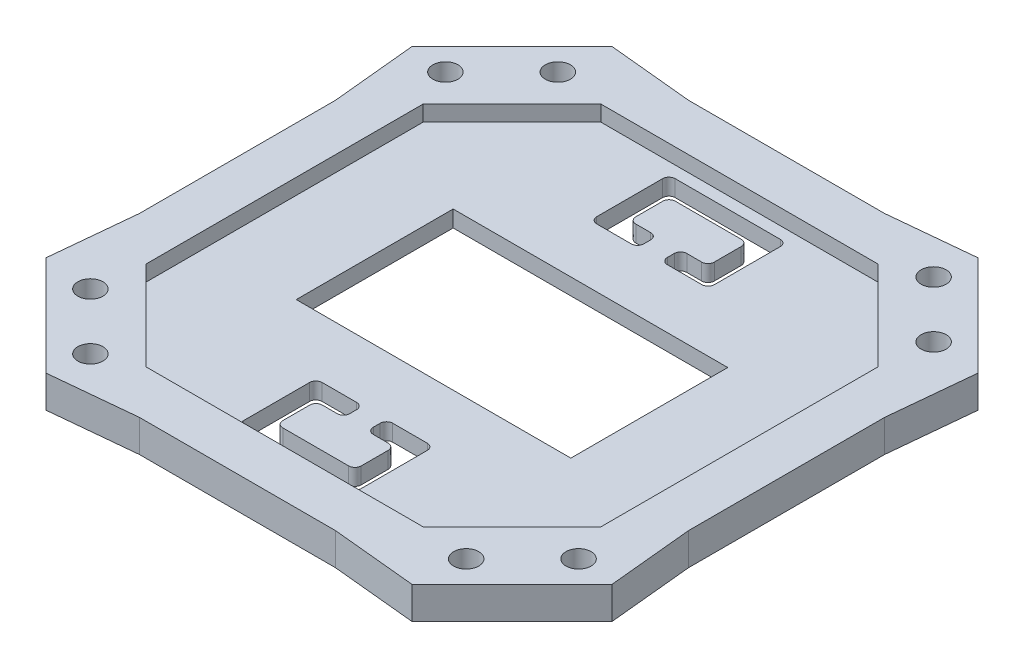
SolidWorks part; units mm, degrees
ref_plane "Front Plane" through (0, 0, 0) normal (0, 0, 1) x (1, 0, 0)
ref_plane "Top Plane" through (0, 0, 0) normal (0, 1, 0) x (1, 0, 0)
ref_plane "Right Plane" through (0, 0, 0) normal (1, 0, 0) x (0, 0, -1)
sketch "Sketch1" plane through (0, 0, 0) normal (0, 1, 0) x (1, 0, 0)
  line L0 (0, 0) -> (84.8528, 84.8528) construction
  line L1 (35, -35) -> (-35, -35) construction
  line L2 (35, -35) -> (35, 35) construction
  line L3 (35, 35) -> (-35, 35) construction
  line L4 (-35, -35) -> (-35, 35) construction
  line L5 (35, -35) -> (-35, 35) construction
  line L6 (35, 35) -> (-35, -35) construction
  line L7 (0, 35) -> (0, -35) construction
  line L8 (-12.5, 35) -> (12.5, 35)
  line L9 (35, 12.5) -> (35, -12.5)
  line L10 (12.5, -35) -> (-12.5, -35)
  line L11 (-35, -12.5) -> (-35, 12.5)
  line L12 (20.5061, 33.234) -> (33.234, 20.5061) construction
  line L13 (23.3345, 36.0624) -> (36.0624, 23.3345)
  line L14 (12.5, 35) -> (23.3345, 36.0624)
  line L15 (36.0624, 23.3345) -> (35, 12.5)
  line L16 (36.0624, -23.3345) -> (23.3345, -36.0624)
  line L17 (35, -12.5) -> (36.0624, -23.3345)
  line L18 (23.3345, -36.0624) -> (12.5, -35)
  line L19 (-23.3345, -36.0624) -> (-36.0624, -23.3345)
  line L20 (-12.5, -35) -> (-23.3345, -36.0624)
  line L21 (-36.0624, -23.3345) -> (-35, -12.5)
  line L22 (-36.0624, 23.3345) -> (-23.3345, 36.0624)
  line L23 (-35, 12.5) -> (-36.0624, 23.3345)
  line L24 (-23.3345, 36.0624) -> (-12.5, 35)
  circle A0 centre (22.6274, 31.1127) radius 1.6
  circle A1 centre (29.7906, 23.9496) radius 1.6
  circle A2 centre (31.1127, -22.6274) radius 1.6
  circle A3 centre (23.9496, -29.7906) radius 1.6
  circle A4 centre (-22.6274, -31.1127) radius 1.6
  circle A5 centre (-29.7906, -23.9496) radius 1.6
  circle A6 centre (-31.1127, 22.6274) radius 1.6
  circle A7 centre (-23.9496, 29.7906) radius 1.6
  point P0 (0, 0)
  dimension "D7" = 3.2
  dimension "D8" = 6
  dimension "D1" = 70
  dimension "D2" = 70
  dimension "D3" = 120
  dimension "D4" = 25
  dimension "D5" = 12.5
  dimension "D9" = 82
  dimension "D10" = 4
  dimension "D11" = 18
  dimension "D12" = 4.1302
  dimension "D6" = 4
  dimension "D13" = 4
extrude "Boss-Extrude2" add sketch "Sketch1" along normal blind 4.1
sketch "Sketch2" plane through (0, 4.1, 0) normal (0, 1, 0) x (1, 0, 0)
  line L0 (0, 35) -> (0, 0) construction
  line L1 (0, 0) -> (-35, 0) construction
  line L2 (-35, -12.5) -> (-35, 12.5) construction
  line L3 (-17.669, 29) -> (17.669, 29)
  line L4 (17.669, 29) -> (29, 17.669)
  line L5 (29, 17.669) -> (29, -17.669)
  line L6 (29, -17.669) -> (17.669, -29)
  line L7 (17.669, -29) -> (-17.669, -29)
  line L8 (-17.669, -29) -> (-29, -17.669)
  line L9 (-29, -17.669) -> (-29, 17.669)
  line L10 (-29, 17.669) -> (-17.669, 29)
  line L12 (-23.3345, -36.0624) -> (-36.0624, -23.3345) construction
  line L13 (23.3345, 36.0624) -> (36.0624, 23.3345) construction
  line L14 (36.0624, -23.3345) -> (23.3345, -36.0624) construction
  line L16 (-36.0624, 23.3345) -> (-23.3345, 36.0624) construction
  line L17 (12.5, -35) -> (-12.5, -35) construction
  line L18 (-12.5, 35) -> (12.5, 35) construction
  dimension "D1" = 6
  dimension "D2" = 9
extrude "Cut-Extrude1" cut sketch "Sketch2" against normal blind 2
sketch "Sketch4" plane through (0, 2.1, 0) normal (0, 1, 0) x (1, 0, 0)
  line L0 (0, 29) -> (0, 0) construction
  line L1 (17.669, 29) -> (-17.669, 29) construction
  line L2 (0, 0) -> (-29, 0) construction
  line L3 (-29, 17.669) -> (-29, -17.669) construction
  line L4 (-24.0792, 13.5676) -> (-16.0792, 6.8995)
  line L5 (-15, 4.5951) -> (-15, -4.5951)
  line L6 (-16.0792, -6.8995) -> (-24.0792, -13.5676)
  line L7 (-29, -11.2631) -> (-29, 11.2631)
  line L8 (-6.8995, 16.0792) -> (-13.5676, 24.0792)
  line L9 (4.5951, 15) -> (-4.5951, 15)
  line L10 (13.5676, 24.0792) -> (6.8995, 16.0792)
  line L11 (-11.2631, 29) -> (11.2631, 29)
  line L12 (16.0792, 6.8995) -> (24.0792, 13.5676)
  line L13 (15, -4.5951) -> (15, 4.5951)
  line L14 (24.0792, -13.5676) -> (16.0792, -6.8995)
  line L15 (29, 11.2631) -> (29, -11.2631)
  line L16 (6.8995, -16.0792) -> (13.5676, -24.0792)
  line L17 (-4.5951, -15) -> (4.5951, -15)
  line L18 (-13.5676, -24.0792) -> (-6.8995, -16.0792)
  line L19 (11.2631, -29) -> (-11.2631, -29)
  arc A0 (-15, -4.5951) -> (-16.0792, -6.8995) centre (-18, -4.5951) cw
  arc A1 (-16.0792, 6.8995) -> (-15, 4.5951) centre (-18, 4.5951) cw
  arc A2 (-24.0792, -13.5676) -> (-29, -11.2631) centre (-26, -11.2631) cw
  arc A3 (-24.0792, 13.5676) -> (-29, 11.2631) centre (-26, 11.2631) ccw
  arc A4 (-4.5951, 15) -> (-6.8995, 16.0792) centre (-4.5951, 18) cw
  arc A5 (6.8995, 16.0792) -> (4.5951, 15) centre (4.5951, 18) cw
  arc A6 (13.5676, 24.0792) -> (11.2631, 29) centre (11.2631, 26) ccw
  arc A7 (-13.5676, 24.0792) -> (-11.2631, 29) centre (-11.2631, 26) cw
  arc A8 (15, 4.5951) -> (16.0792, 6.8995) centre (18, 4.5951) cw
  arc A9 (16.0792, -6.8995) -> (15, -4.5951) centre (18, -4.5951) cw
  arc A10 (24.0792, -13.5676) -> (29, -11.2631) centre (26, -11.2631) ccw
  arc A11 (24.0792, 13.5676) -> (29, 11.2631) centre (26, 11.2631) cw
  arc A12 (4.5951, -15) -> (6.8995, -16.0792) centre (4.5951, -18) cw
  arc A13 (-6.8995, -16.0792) -> (-4.5951, -15) centre (-4.5951, -18) cw
  arc A14 (-13.5676, -24.0792) -> (-11.2631, -29) centre (-11.2631, -26) ccw
  arc A15 (13.5676, -24.0792) -> (11.2631, -29) centre (11.2631, -26) cw
  point P16 (-15, -6)
  point P19 (-15, 6)
  point P22 (-29, -17.669)
  point P25 (-29, 17.669)
  dimension "D4" = 3
  dimension "D1" = 12
  dimension "D2" = 15
  dimension "D3" = 6
  dimension "D5" = 4
extrude "Cut-Extrude2" [suppressed] cut sketch "Sketch4" against normal blind 1.5
sketch "Sketch6" plane through (0, 2.1, 0) normal (0, 1, 0) x (1, 0, 0)
  line L0 (0, 0) -> (84.8528, 84.8528) construction
  line L1 (0, 0) -> (15.25, 0) construction
  line L2 (0, 0) -> (0, 15.25) construction
  line L3 (0, 15.25) -> (15.25, 15.25) construction
  line L4 (15.25, 0) -> (15.25, 15.25) construction
  circle A0 centre (15.25, 15.25) radius 1.5
  dimension "D2" = 3
  dimension "D1" = 15.25
extrude "Cut-Extrude3" [suppressed] cut sketch "Sketch6" against normal through all contours A0
sketch "Sketch7" [suppressed] plane through (0, 2, 0) normal (0, 1, 0) x (1, 0, 0)
  circle A0 centre (15.25, 15.25) radius 4
  circle A1 centre (15.25, 15.25) radius 1.5 construction
  circle A2 centre (15.25, 15.25) radius 1.5
  dimension "D1" = 8
extrude "Boss-Extrude3" [suppressed] add sketch "Sketch7" along normal blind 1.5
ref_axis "Axis1" [suppressed] through (0, 4.2, 0) along (0, -1, 0)
pattern_circular "CirPattern1" [suppressed] count 4 over 360 about axis through (0, 4.2, 0) along (0, -1, 0) of bodies 106
fillet "Fillet1" [suppressed] radius 2
sketch "Sketch8" plane through (0, 2.1, 0) normal (0, 1, 0) x (1, 0, 0)
  line L0 (0, -29) -> (0, 29) construction
  line L2 (0, 0) -> (-23.4448, 0) construction
  line L3 (17.669, 29) -> (-17.669, 29) construction
  line L9 (-1.5, 19.1817) -> (-1.5, 18.3)
  line L14 (-6.7, 27.5) -> (6.7, 27.5)
  line L15 (-7.5, 26.7) -> (-7.5, 18.3)
  line L16 (-6.7, 17.5) -> (-2.3, 17.5)
  line L17 (7.5, 26.7) -> (7.5, 18.3)
  line L18 (-7.5, 27.5) -> (7.5, 17.5) construction
  line L19 (-7.5, 17.5) -> (7.5, 27.5) construction
  line L20 (-4.2, 25.0183) -> (4.2, 25.0183)
  line L21 (-5, 24.2183) -> (-5, 20.7817)
  line L22 (-4.2, 19.9817) -> (-2.3, 19.9817)
  line L23 (5, 24.2183) -> (5, 20.7817)
  line L24 (-5, 25.0183) -> (5, 19.9817) construction
  line L25 (-5, 19.9817) -> (5, 25.0183) construction
  line L26 (1.5, 19.1817) -> (1.5, 18.3)
  line L27 (2.3, 19.9817) -> (4.2, 19.9817)
  line L28 (2.3, 17.5) -> (6.7, 17.5)
  line L29 (-5, -19.9817) -> (5, -25.0183) construction
  line L30 (-5, -25.0183) -> (5, -19.9817) construction
  line L31 (-7.5, -17.5) -> (7.5, -27.5) construction
  line L32 (-7.5, -27.5) -> (7.5, -17.5) construction
  line L33 (2.3, -17.5) -> (6.7, -17.5)
  line L34 (2.3, -19.9817) -> (4.2, -19.9817)
  line L35 (1.5, -19.1817) -> (1.5, -18.3)
  line L36 (5, -24.2183) -> (5, -20.7817)
  line L37 (-4.2, -19.9817) -> (-2.3, -19.9817)
  line L38 (-5, -24.2183) -> (-5, -20.7817)
  line L39 (-4.2, -25.0183) -> (4.2, -25.0183)
  line L40 (7.5, -26.7) -> (7.5, -18.3)
  line L41 (-6.7, -17.5) -> (-2.3, -17.5)
  line L42 (-7.5, -26.7) -> (-7.5, -18.3)
  line L43 (-6.7, -27.5) -> (6.7, -27.5)
  line L44 (-1.5, -19.1817) -> (-1.5, -18.3)
  arc A0 (1.5, 18.3) -> (2.3, 17.5) centre (2.3, 18.3) ccw
  arc A1 (1.5, 19.1817) -> (2.3, 19.9817) centre (2.3, 19.1817) cw
  arc A2 (-1.5, 18.3) -> (-2.3, 17.5) centre (-2.3, 18.3) cw
  arc A3 (4.2, 25.0183) -> (5, 24.2183) centre (4.2, 24.2183) cw
  arc A4 (-5, 20.7817) -> (-4.2, 19.9817) centre (-4.2, 20.7817) ccw
  arc A5 (-4.2, 25.0183) -> (-5, 24.2183) centre (-4.2, 24.2183) ccw
  arc A10 (4.2, 19.9817) -> (5, 20.7817) centre (4.2, 20.7817) ccw
  arc A11 (-1.5, 19.1817) -> (-2.3, 19.9817) centre (-2.3, 19.1817) ccw
  arc A12 (6.7, 27.5) -> (7.5, 26.7) centre (6.7, 26.7) cw
  arc A13 (-7.5, 18.3) -> (-6.7, 17.5) centre (-6.7, 18.3) ccw
  arc A14 (-6.7, 27.5) -> (-7.5, 26.7) centre (-6.7, 26.7) ccw
  arc A15 (6.7, 17.5) -> (7.5, 18.3) centre (6.7, 18.3) ccw
  arc A16 (6.7, -17.5) -> (7.5, -18.3) centre (6.7, -18.3) cw
  arc A17 (-6.7, -27.5) -> (-7.5, -26.7) centre (-6.7, -26.7) cw
  arc A18 (-7.5, -18.3) -> (-6.7, -17.5) centre (-6.7, -18.3) cw
  arc A19 (6.7, -27.5) -> (7.5, -26.7) centre (6.7, -26.7) ccw
  arc A20 (-1.5, -19.1817) -> (-2.3, -19.9817) centre (-2.3, -19.1817) cw
  arc A21 (4.2, -19.9817) -> (5, -20.7817) centre (4.2, -20.7817) cw
  arc A22 (-4.2, -25.0183) -> (-5, -24.2183) centre (-4.2, -24.2183) cw
  arc A23 (-5, -20.7817) -> (-4.2, -19.9817) centre (-4.2, -20.7817) cw
  arc A24 (4.2, -25.0183) -> (5, -24.2183) centre (4.2, -24.2183) ccw
  arc A25 (-1.5, -18.3) -> (-2.3, -17.5) centre (-2.3, -18.3) ccw
  arc A26 (1.5, -19.1817) -> (2.3, -19.9817) centre (2.3, -19.1817) ccw
  arc A27 (1.5, -18.3) -> (2.3, -17.5) centre (2.3, -18.3) cw
  point P0 (0, 22.5)
  point P12 (0, 22.5)
  point P22 (1.5, 17.5)
  point P25 (1.5, 19.9817)
  point P28 (-1.5, 17.5)
  point P43 (-1.5, 19.9817)
  point P101 (-1.5, -19.9817)
  point P102 (-1.5, -17.5)
  point P103 (1.5, -19.9817)
  point P104 (1.5, -17.5)
  point P105 (0, -22.5)
  dimension "D6" = 0.8
  dimension "D1" = 17.5
  dimension "D2" = 10
  dimension "D3" = 15
  dimension "D4" = 2.5
  dimension "D5" = 6
extrude "Cut-Extrude4" cut sketch "Sketch8" against normal through all
sketch "Sketch9" plane through (0, 2.1, 0) normal (0, 1, 0) x (1, 0, 0)
  line L0 (35, -35) -> (-35, 35) construction
  line L1 (-17.5, 10) -> (17.5, 10)
  line L2 (-17.5, 10) -> (-17.5, -10)
  line L3 (-17.5, -10) -> (17.5, -10)
  line L4 (17.5, 10) -> (17.5, -10)
  line L5 (-17.5, 10) -> (17.5, -10) construction
  line L6 (-17.5, -10) -> (17.5, 10) construction
  point P0 (0, 0)
  dimension "D1" = 35
  dimension "D2" = 20
extrude "Cut-Extrude5" cut sketch "Sketch9" against normal blind 10
